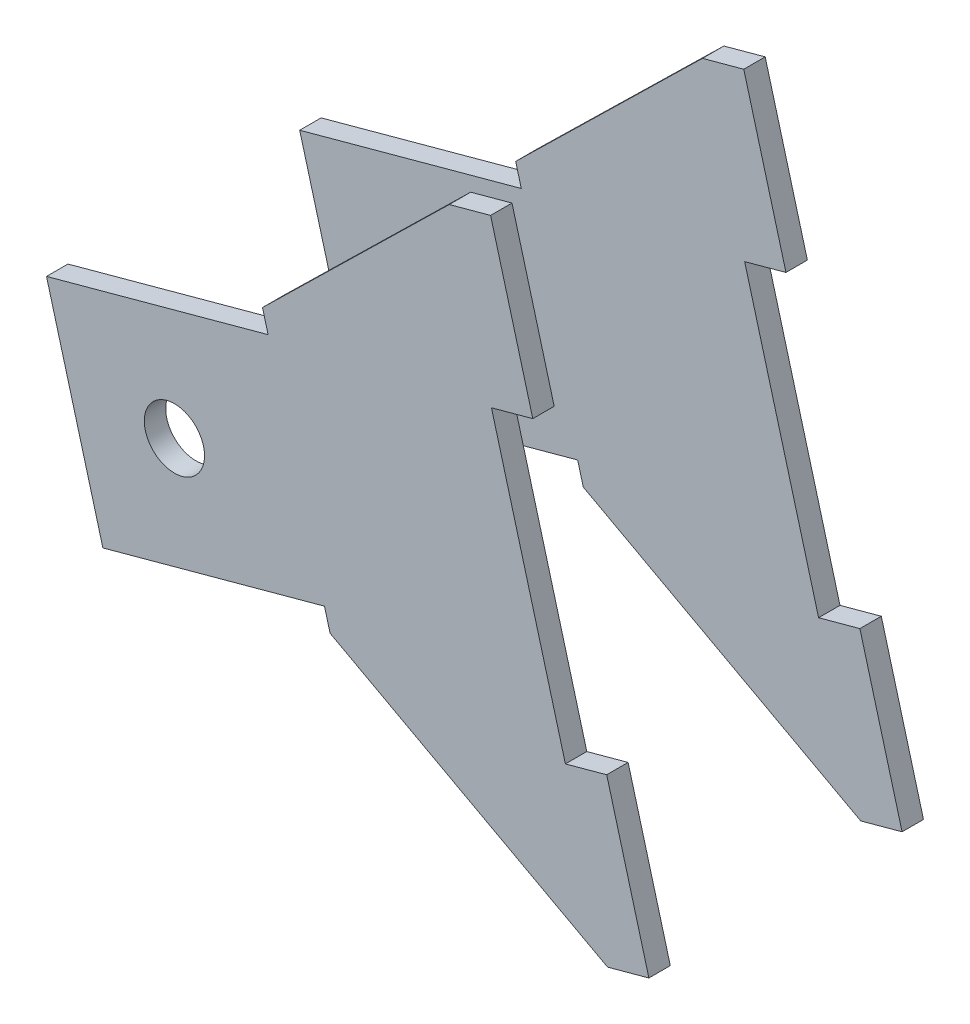
SolidWorks part; units mm, degrees
material "Gillfab4009"
ref_plane "Front Plane" through (0, 0, 0) normal (0, 0, 1) x (1, 0, 0)
ref_plane "Top Plane" through (0, 0, 0) normal (0, 1, 0) x (1, 0, 0)
ref_plane "Right Plane" through (0, 0, 0) normal (1, 0, 0) x (0, 0, -1)
sketch "Sketch1" plane through (2328.5898, 466.462, -4.004) normal (0, 0, 1) x (0.9649, 0.2628, 0)
  line L1 (-2161.2189, 236.8927) -> (-2270.2189, 236.8927)
  line L2 (-2270.2189, 236.8927) -> (-2270.2189, 135.0855)
  line L3 (-2270.2189, 135.0855) -> (-2161.2189, 135.0855)
  line L5 (-2052.9116, 85.557) -> (-2052.9116, 9.357) construction
  line L6 (-2161.2189, 236.8927) -> (-2161.2189, 135.0855) construction
  line L7 (-2222.2031, 135.0855) -> (-2220.1272, 236.8927) construction
  line L8 (-2052.9116, 231.1773) -> (-2052.9116, 97.657)
  line L9 (-2161.2189, 135.0855) -> (-2161.2189, 124.9255)
  line L10 (-2161.2189, 124.9255) -> (-2052.9116, 21.457)
  line L11 (-2161.2189, 236.8927) -> (-2161.2189, 247.0527)
  line L12 (-2161.2189, 247.0527) -> (-2052.9116, 307.3773)
  line L13 (-2052.9116, 307.3773) -> (-2032.5916, 307.3773)
  line L14 (-2032.5916, 307.3773) -> (-2032.5916, 231.1773)
  line L15 (-2032.5916, 231.1773) -> (-2052.9116, 231.1773)
  line L16 (-2052.9116, 21.457) -> (-2032.5916, 21.457)
  line L17 (-2032.5916, 21.457) -> (-2032.5916, 97.657)
  line L18 (-2032.5916, 97.657) -> (-2052.9116, 97.657)
  line L19 (-2052.9116, 97.657) -> (-2052.9116, 21.457) construction
  circle A0 centre (-2221.1651, 185.9891) radius 9.5377 construction
  circle A1 centre (-2221.1651, 185.9891) radius 9.5377 construction
  circle A2 centre (-2352.5682, 163.2853) radius 151.5212 construction
  circle A3 centre (-2221.1651, 185.9891) radius 14.2875
  point P17 (-2221.1651, 185.9891)
  dimension "D1" = 28.575
  dimension "D2" = 113.6285
  dimension "D3" = 108.3073
  dimension "D4" = 10.16
  dimension "D5" = 215.4357
  dimension "D6" = 10.16
  dimension "D7" = 285.9203
  dimension "D8" = 109
  dimension "D9" = 76.2
  dimension "D10" = 20.32
  dimension "D11" = 76.2
extrude "Boss-Extrude1" add sketch "Sketch1" along normal blind 10.16 from offset 90 offset against normal yes
extrude "Boss-Extrude2" add sketch "Sketch1<2>" along normal blind 10.16 from offset 210.16 separate body offset against normal yes
sketch "Sketch1<2>" plane through (2328.5898, 466.462, -4.004) normal (0, 0, 1) x (0.9649, 0.2628, 0) same geometry as "Sketch1"
